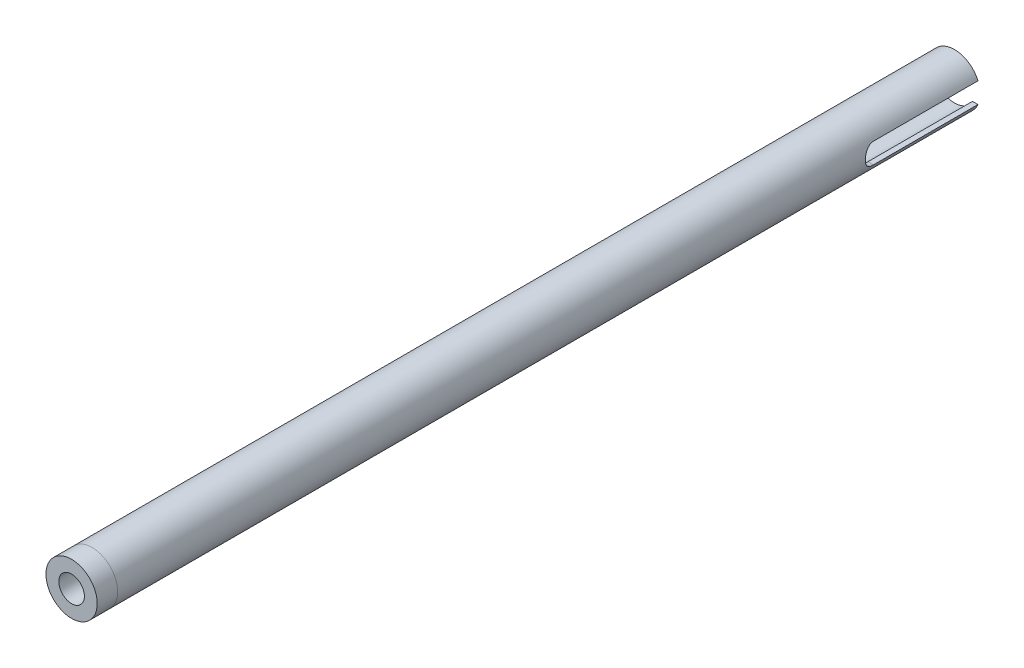
SolidWorks part; units mm, degrees
material "AISI 4130 Steel, annealed at 865C"
ref_plane "Front Plane" through (0, 0, 0) normal (0, 0, 1) x (1, 0, 0)
ref_plane "Top Plane" through (0, 0, 0) normal (0, 1, 0) x (1, 0, 0)
ref_plane "Right Plane" through (0, 0, 0) normal (1, 0, 0) x (0, 0, -1)
sketch "Axis" plane through (0, 0, 0) normal (0, 1, 0) x (1, 0, 0)
  line L0 (0, 0) -> (0, 273.4854) construction
  line L1 (0, 0) -> (0, -28.575) construction
  line L2 (0, 273.4854) -> (-7.9375, 273.4854) construction
  line L3 (0, 294.3429) -> (-10.3187, 267.2281) construction
  dimension "D1" = 28.575
  dimension "D2" = 7.9375
sketch "Sketch1" plane through (0, 0, 0) normal (0, 0, 1) x (1, 0, 0)
  line L0 (-7.9375, 0) -> (7.9375, 0) construction
  line L1 (-7.2748, 3.175) -> (7.2748, 3.175)
  line L2 (-7.2748, -3.175) -> (7.2748, -3.175)
  circle A0 centre (0, 0) radius 7.9375
  circle A1 centre (0, 0) radius 6.4135
  circle A2 centre (0, 0) radius 3.9688
  dimension "D1" = 15.875
  dimension "D3" = 7.9375
  dimension "D2" = 1.524
  dimension "D4" = 6.35
extrude "Threaded insert 1-1" add sketch "Sketch1" against normal blind 6.35 contours A2 L1 A1 | A1 L1 A0 | A2 L0 A1 L1 | A1 L0 A0 L1 | L0 A1 L2 A0 | L0 A2 L2 A1 | A2 L2 A1 | A1 L2 A0 | L0 A1 L2 A2 | L0 A0 L2 A1 | A0 L0 A1 L1 | A1 L0 A2 L1 region at (4.7887, 1.6543, 0) region at (4.7887, -1.6543, 0) region at (6.9234, 1.6163, 0) region at (6.9234, -1.6163, 0) region at (-4.7887, -1.6543, 0) region at (-4.7887, 1.6543, 0) region at (0, 4.6159, 0) region at (0, -4.6159, 0) region at (0, 6.5666, 0) region at (6.4237, -3.3281, 0) region at (-6.9234, -1.6163, 0) region at (-6.9234, 1.6163, 0)
extrude "Threaded insert 1-2" add sketch "Sketch1<3>" against normal blind 9.525 from surface contours A2 L1 A1 | A2 L0 A1 L1 | L0 A2 L2 A1 | A2 L2 A1 | L0 A1 L2 A2 | A1 L0 A2 L1 region at (4.7887, 1.6543, 0) region at (4.7887, -1.6543, 0) region at (-4.7887, -1.6543, 0) region at (-4.7887, 1.6543, 0) region at (0, 4.6159, 0) region at (0, -4.6159, 0) starting at face at (7.9375, 0, -6.35)
sketch "Sketch1<3>" plane through (0, 0, 0) normal (0, 0, 1) x (1, 0, 0) same geometry as "Sketch1"
extrude "A-arm tube" add sketch "Sketch1<4>" against normal up to vertex (273.4854 mm away) from surface separate body contours A1 L1 A0 | A1 L0 A0 L1 | L0 A1 L2 A0 | A1 L2 A0 | L0 A0 L2 A1 | A0 L0 A1 L1 region at (6.9234, 1.6163, 0) region at (6.9234, -1.6163, 0) region at (0, 6.5666, 0) region at (6.4237, -3.3281, 0) region at (-6.9234, -1.6163, 0) region at (-6.9234, 1.6163, 0) up to point (0, 0, -273.4854) starting at face at (6.4135, 0, -6.35)
sketch "Sketch1<4>" plane through (0, 0, 0) normal (0, 0, 1) x (1, 0, 0) same geometry as "Sketch1"
extrude "Apex slot" cut sketch "Sketch1<5>" along normal blind 35.56 from surface contours A0 L0 A1 L1 | L0 A0 L2 A1 | A1 L0 A0 L1 | L0 A1 L2 A0 region at (6.9234, 1.6163, 0) region at (6.9234, -1.6163, 0) region at (-6.9234, -1.6163, 0) region at (-6.9234, 1.6163, 0) starting at face at (6.4135, 0, -273.4854)
sketch "Sketch1<5>" plane through (0, 0, 0) normal (0, 0, 1) x (1, 0, 0) same geometry as "Sketch1"
fillet "Fillet1" radius 3.175 4 edges at (-6.4237, 3.175, -237.9254) (-6.4237, -3.175, -237.9254) (6.4237, -3.175, -237.9254) (6.4237, 3.175, -237.9254)
equation "\"tube diameter\"= 5 / 8"
equation "\"tube thickness\"= .06"
equation "\"apex thickness\"= .25"
equation "\"tube slot\"= 1.4"
equation "\"D1@Sketch1\"=\"tube diameter\""
equation "\"D2@Sketch1\"=\"tube thickness\""
equation "\"threaded insert hole\"= .3125"
equation "\"D3@Sketch1\"=\"threaded insert hole\""
equation "\"D4@Sketch1\"=\"apex thickness\""
equation "\"D1@Apex slot\" = \"tube slot\""
equation "\"D1@Fillet1\"=\"apex thickness\"/2"
